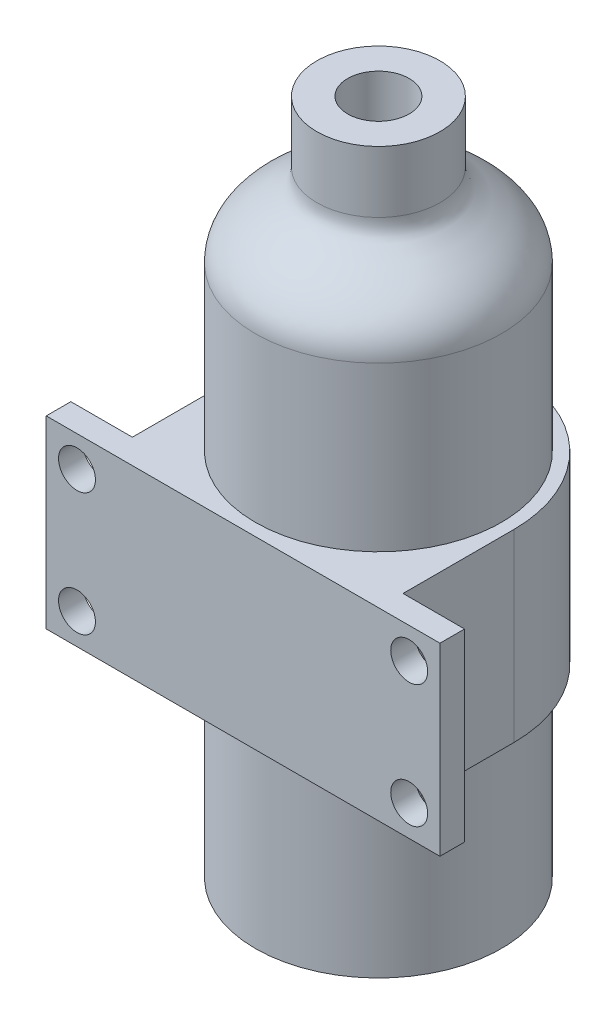
SolidWorks part; units mm, degrees
ref_plane "Alzado" through (0, 0, 0) normal (0, 0, 1) x (1, 0, 0)
ref_plane "Planta" through (0, 0, 0) normal (0, 1, 0) x (1, 0, 0)
ref_plane "Vista lateral" through (0, 0, 0) normal (1, 0, 0) x (0, 0, -1)
sketch "Croquis3" plane through (0, 0, 0) normal (0, 0, 1) x (1, 0, 0)
  line L0 (0, 0) -> (0, 50) construction
  line L1 (0, 50) -> (5, 50) construction
  line L3 (10, 43.2783) -> (10, 0)
  line L4 (10, 0) -> (0, 0)
  line L5 (0, 0) -> (0, 50)
  line L6 (0, 50) -> (5, 50)
  line L7 (10, 42.3793) -> (10, 44.6739) construction
  line L8 (5, 48.1941) -> (5, 49.7862) construction
  spline S0 degree 3 poles (5, 50) (5, 49.0049) (5.6792, 48.3381) (8.8641, 46.2963) (10, 44.7125) (10, 43.2783) knots 0 0 0 0 0.19722 0.426407 1 1 1 1
  point P5 (3.0224, 48.4845)
  point P6 (7.343, 37.9383)
  point P10 (5.5012, 42.0379)
  point P11 (3.5405, 44.5927)
  point P12 (4.4317, 44.1173)
  point P13 (3.0136, 46.7214)
  point P14 (4.0485, 45.5964)
  point P15 (7.2657, 43.5266)
  point P20 (3.1486, 46.2489)
  point P21 (4.8317, 45.644)
  point P22 (3.5453, 46.232)
  point P23 (3.358, 47.5802)
  point P24 (4.7247, 47.3452)
  point P25 (3.2804, 47.6856)
  point P26 (6.905, 46.066)
  point P27 (4.2169, 48.1709)
  point P28 (3.4774, 48.5407)
  point P29 (6.4456, 47.866)
  point P30 (5.6085, 48.4241)
  point P31 (6.7973, 47.7861)
  point P32 (5.4677, 48.5705)
  point P33 (7.0499, 47.7994)
  point P34 (7.0898, 47.693)
  point P35 (5.7735, 48.3445)
  point P36 (10, 43.2783)
  point P37 (7.6514, 47.004)
  dimension "D1" = 50
  dimension "D2" = 10
  dimension "D3" = 5
revolve "Revolución2" add sketch "Croquis3" angle 360 about L5
sketch "Croquis4" plane through (0, 50, 0) normal (0, 1, 0) x (1, 0, 0)
  circle A0 centre (0, 0) radius 5
  dimension "D1" = 10
extrude "Saliente-Extruir1" add sketch "Croquis4" along normal blind 5
sketch "Croquis5" plane through (0, 55, 0) normal (0, 1, 0) x (1, 0, 0)
  circle A0 centre (0, 0) radius 2.5
  dimension "D1" = 5
extrude "Cortar-Extruir1" cut sketch "Croquis5" against normal blind 10
shell "Vaciado2" thickness 2 removed face at (0, 45, 2.5)
ref_plane "Plano1" through (0, 22.5, 0) normal (0, 1, 0) x (1, 0, 0)
sketch "Croquis6" plane through (0, 22.5, 0) normal (0, 1, 0) x (1, 0, 0)
  line L0 (-11, 0) -> (-11, -9)
  line L1 (-11, -9) -> (-16, -9)
  line L2 (-16, -9) -> (-16, -11)
  line L3 (-16, -11) -> (16, -11)
  line L4 (16, -11) -> (16, -9)
  line L5 (16, -9) -> (11, -9)
  line L6 (11, -9) -> (11, 0)
  circle A0 centre (0, 0) radius 9
  arc A1 (11, 0) -> (-11, 0) centre (0, 0) ccw
  dimension "D1" = 18
  dimension "D2" = 22
  dimension "D3" = 2
  dimension "D4" = 5
extrude "Saliente-Extruir2" add sketch "Croquis6" along normal mid plane 15
sketch "Croquis7" plane through (0, 0, 9) normal (0, 0, -1) x (-1, 0, 0)
  line L0 (16, 22.5) -> (-16, 22.5) construction
  line L1 (16, 30) -> (16, 15) construction
  line L2 (-16, 30) -> (-16, 15) construction
  line L3 (-13.5, 17.5) -> (-13.5, 27.5) construction
  line L4 (13.5, 17.5) -> (13.5, 27.5) construction
  circle A0 centre (-13.5, 27.5) radius 1.5
  circle A1 centre (-13.5, 17.5) radius 1.5
  circle A2 centre (13.5, 17.5) radius 1.5
  circle A3 centre (13.5, 27.5) radius 1.5
  point P9 (-13.5, 22.5)
  point P12 (13.5, 22.5)
  dimension "D4" = 3
  dimension "D1" = 10
  dimension "D2" = 2.5
  dimension "D3" = 2.5
extrude "Cortar-Extruir2" cut sketch "Croquis7" against normal through all
